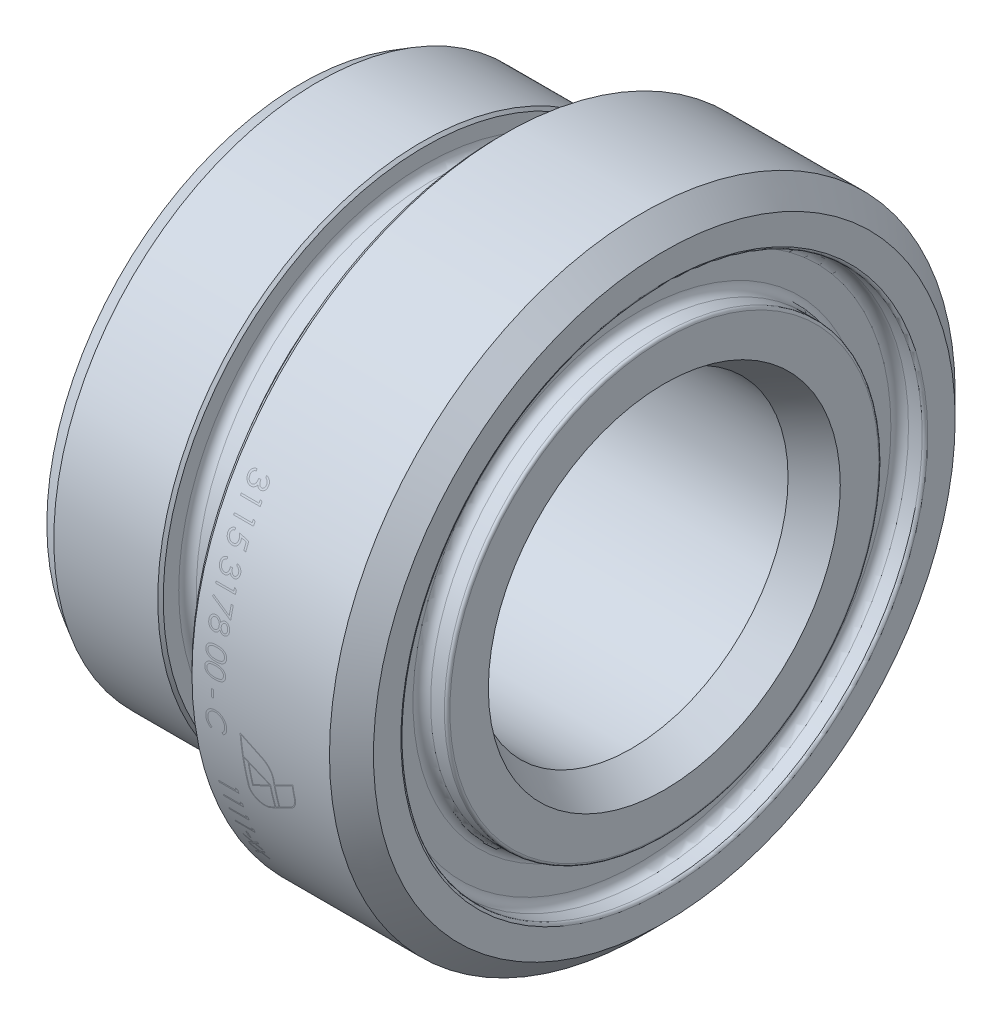
SolidWorks part; units mm, degrees
material "17CrNiMo6"
ref_plane "Front Plane" through (0, 0, 0) normal (0, 0, 1) x (1, 0, 0)
ref_plane "Top Plane" through (0, 0, 0) normal (0, 1, 0) x (1, 0, 0)
ref_plane "Right Plane" through (0, 0, 0) normal (1, 0, 0) x (0, 0, -1)
sketch "Sketch1" plane through (0, 0, 0) normal (0, 0, 1) x (1, 0, 0)
  line L0 (0, 16) -> (0, 19.75)
  line L1 (0, 19.75) -> (-1.5, 19.75)
  line L2 (-2.3, 20.55) -> (-2.3, 22.9)
  line L3 (-1.5, 23.7) -> (0, 23.7)
  line L4 (0, 23.7) -> (0, 26.445)
  line L5 (0, 26.445) -> (-2, 28.445)
  line L6 (-2, 28.445) -> (-15, 28.445)
  line L7 (-15, 28.445) -> (-15, 24.461)
  line L8 (-16.9, 24.01) -> (-18, 24.01)
  line L9 (-31.5, 24.01) -> (-33, 23.144)
  line L10 (-33, 23.144) -> (-33, 20.025)
  line L11 (-33, 20.025) -> (-26.8, 20.025)
  line L12 (-26, 19.225) -> (-26, 15.275)
  line L13 (-24.5, 14.25) -> (-3, 14.25)
  line L14 (-3, 14.25) -> (0, 16)
  line L15 (0, 0) -> (-33, 0) construction
  line L16 (-21.8, 24.01) -> (-21.8, 22.35)
  line L17 (-21, 21.55) -> (-18.8, 21.55)
  line L18 (-18, 22.35) -> (-18, 24.01)
  line L19 (-21.8, 24.01) -> (-31.5, 24.01)
  line L20 (-26, 15.275) -> (-24.5, 15.275)
  line L21 (-24.5, 15.275) -> (-24.5, 14.25)
  line L22 (-16.9, 24.01) -> (-16.0736, 23.7092)
  arc A0 (-16.0736, 23.7092) -> (-15, 24.461) centre (-15.8, 24.461) ccw
  arc A1 (-26.8, 20.025) -> (-26, 19.225) centre (-26.8, 19.225) cw
  arc A2 (-2.3, 22.9) -> (-1.5, 23.7) centre (-1.5, 22.9) cw
  arc A3 (-1.5, 19.75) -> (-2.3, 20.55) centre (-1.5, 20.55) cw
  arc A4 (-18.8, 21.55) -> (-18, 22.35) centre (-18.8, 22.35) ccw
  arc A5 (-21.8, 22.35) -> (-21, 21.55) centre (-21, 22.35) ccw
  dimension "D22" = 0.8
  dimension "D25" = 0.8
  dimension "D1" = 33
  dimension "D2" = 15
  dimension "D3" = 28.5
  dimension "D4" = 40.05
  dimension "D5" = 56.89
  dimension "D6" = 48.02
  dimension "D7" = 1.5
  dimension "D8" = 30
  dimension "D9" = 7
  dimension "D10" = 32
  dimension "D11" = 3
  dimension "D12" = 39.5
  dimension "D13" = 47.4
  dimension "D14" = 2.3
  dimension "D15" = 2
  dimension "D16" = 45
  dimension "D17" = 15
  dimension "D18" = 3.8
  dimension "D19" = 1.5
  dimension "D20" = 30.55
  dimension "D21" = 43.1
  dimension "D23" = 20
  dimension "D24" = 1.9
revolve "Revolve1" add sketch "Sketch1" angle 360 about L15
cosmetic thread "Cosmetic Thread1" parameters "D1"=14, "D2"=30
chamfer "Chamfer1" distance 0.5 angle 45 1 edges at (-15, 0, -28.445)
fillet "Fillet1" radius 0.25 1 edges at (-24.5, 0, -14.25)
fillet "Fillet2" radius 0.25 2 edges at (0, 0, -19.75) (0, 0, -23.7)
chamfer "Chamfer2" distance 0.25 angle 45 3 edges at (-18, 0, -24.01) (-21.8, 0, -24.01) (-33, 0, -20.025)
sketch "Sketch2" plane through (0, 0, 0) normal (0, 0, 1) x (1, 0, 0)
  line L0 (-13.3238, 20.3889) -> (-13.3238, -21.0896) construction
  text T0 "3115 3178 00 - C      1111-xx" font "Century Gothic" height 1.8
  line B0 (-10.2378, -7.0347) -> (-10.2378, -4.42)
  line B1 (-9.7048, -6.6474) -> (-9.7048, -4.7231)
  line B2 (-10.1578, -4.4655) -> (-9.7848, -4.6776)
  line B3 (-7.4825, -5.4264) -> (-7.4825, -4.9703)
  line B4 (-5.6713, -4.42) -> (-7.4825, -5.4264)
  line B5 (-9.7048, -6.6474) -> (-7.987, -5.6999)
  line B6 (-7.987, -7.8034) -> (-8.4001, -8.0424)
  line B7 (-5.6713, -5.7032) -> (-5.6713, -4.42)
  line B8 (-7.4825, -7.5282) -> (-7.987, -7.8034)
  line B9 (-7.4825, -7.5282) -> (-6.3172, -6.8372)
  line B10 (-10.2378, -4.42) -> (-10.2378, -2.422)
  line B11 (-8.2625, -3.5453) -> (-10.2378, -2.422)
  line B12 (-7.9068, -7.6868) -> (-7.5625, -7.4827)
  line B13 (-5.7513, -5.7032) -> (-5.7513, -4.5559)
  line B14 (-5.7513, -4.5559) -> (-7.4825, -5.5179)
  line B15 (-7.5625, -4.9703) -> (-7.5625, -7.4827)
  line B16 (-8.3039, -3.6138) -> (-10.1578, -2.5595)
  line B17 (-10.1578, -4.3734) -> (-10.1578, -2.5595)
  line B18 (-7.9068, -5.6535) -> (-7.9068, -7.6868)
  line B19 (-10.1578, -4.3734) -> (-7.9068, -5.6535)
  line B20 (-7.987, -7.711) -> (-8.4417, -7.974)
  line B21 (-10.1578, -7.0347) -> (-10.1578, -4.4655)
  line B22 (-7.4825, -5.5179) -> (-7.4825, -7.4352)
  line B23 (-7.4825, -7.4352) -> (-6.358, -6.7684)
  line B24 (-9.7848, -6.7829) -> (-9.7848, -4.6776)
  line B25 (-9.7848, -6.7829) -> (-7.987, -5.7912)
  line B26 (-7.987, -5.7912) -> (-7.987, -7.711)
  line B27 (-9.7048, -4.7231) -> (-7.987, -5.6999)
  arc B28 (-6.3172, -6.8372) -> (-5.6713, -5.7032) centre (-6.9897, -5.7032) ccw
  arc B29 (-10.2378, -7.0347) -> (-8.4001, -8.0424) centre (-9.0427, -7.0347) ccw
  arc B30 (-7.4825, -4.9703) -> (-8.2625, -3.5453) centre (-9.1742, -4.9703) ccw
  arc B31 (-6.358, -6.7684) -> (-5.7513, -5.7032) centre (-6.9897, -5.7032) ccw
  arc B32 (-7.5625, -4.9703) -> (-8.3039, -3.6138) centre (-9.1742, -4.9703) ccw
  arc B33 (-10.1578, -7.0347) -> (-8.4417, -7.974) centre (-9.0427, -7.0347) ccw
  dimension "D1" = 13.3238
sketch_block_instance "SKETCH LOGO-1"
sketch_block "SKETCH LOGO" parameters "D1"=29.059, "D2"=11.4163, "D3"=29.624, "D4"=6.8884
sketch "Sketch3" plane through (0, 0, 0) normal (0, 0, 1) x (1, 0, 0)
  line L0 (-8.8, 28.445) -> (-8.8, 26.9)
  line L1 (-2, 28.445) -> (-15, 28.445) construction
  line L2 (-8, 26.1) -> (-5.8, 26.1)
  line L3 (-5, 26.9) -> (-5, 28.445)
  line L4 (-8.8, 28.445) -> (-5, 28.445)
  line L5 (0, 0) -> (-38.5704, 0) construction
  line L6 (0, 23.7) -> (0, 26.445) construction
  arc A0 (-5.8, 26.1) -> (-5, 26.9) centre (-5.8, 26.9) ccw
  arc A1 (-8.8, 26.9) -> (-8, 26.1) centre (-8, 26.9) ccw
  dimension "D4" = 0.8
  dimension "D1" = 3.8
  dimension "D2" = 52.2
  dimension "D3" = 5
revolve "Cut-Revolve1" [suppressed] cut sketch "Sketch3" angle 360 about L5
chamfer "Chamfer3" [suppressed] distance 0.25 angle 45
wrap "Wrap1" sketch "Sketch2" wrap type scribe source sketch "Sketch2" face at (-14.5, 0, 28.445)
